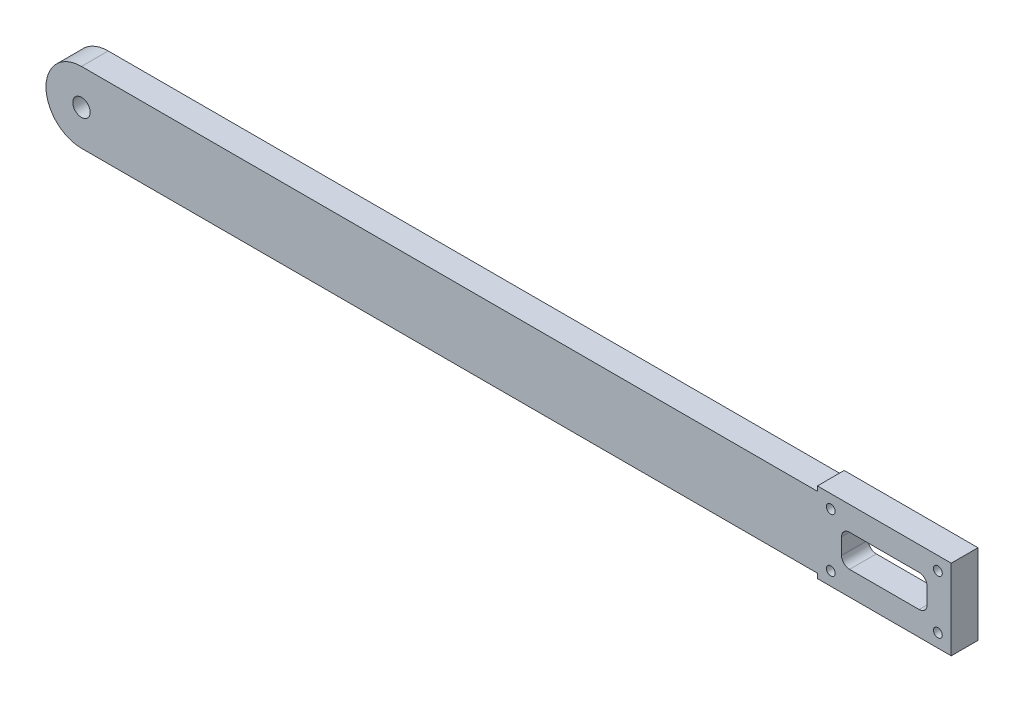
SolidWorks part; units mm, degrees
ref_plane "Front Plane" through (0, 0, 0) normal (0, 0, 1) x (1, 0, 0)
ref_plane "Top Plane" through (0, 0, 0) normal (0, 1, 0) x (1, 0, 0)
ref_plane "Right Plane" through (0, 0, 0) normal (1, 0, 0) x (0, 0, -1)
sketch "Sketch1" plane through (0, 0, 0) normal (0, 0, 1) x (1, 0, 0)
  line L0 (0, 0) -> (300, 0) construction
  line L1 (0, 13.25) -> (300, 13.25)
  line L2 (0, -13.25) -> (300, -13.25)
  line L3 (280, 10) -> (320, 10) construction
  line L4 (275, -15) -> (325, -15)
  line L5 (275, -15) -> (275, 15)
  line L6 (275, 15) -> (325, 15)
  line L7 (325, -15) -> (325, 15)
  line L8 (300, 15) -> (300, -15) construction
  line L9 (275, 0) -> (325, 0) construction
  line L10 (280, 10) -> (280, -10) construction
  line L12 (287, -6) -> (313, -6)
  line L13 (284, -3) -> (284, 3)
  line L14 (287, 6) -> (313, 6)
  line L15 (316, -3) -> (316, 3)
  line L16 (284, -6) -> (316, 6) construction
  line L17 (284, 6) -> (316, -6) construction
  arc A0 (0, 13.25) -> (0, -13.25) centre (0, 0) ccw
  arc A1 (300, -13.25) -> (300, 13.25) centre (300, 0) ccw
  circle A2 centre (0, 0) radius 3.25
  circle A3 centre (280, 10) radius 1.65
  circle A4 centre (320, 10) radius 1.65
  circle A5 centre (280, -10) radius 1.65
  circle A6 centre (320, -10) radius 1.65
  arc A7 (284, 3) -> (287, 6) centre (287, 3) cw
  arc A8 (316, 3) -> (313, 6) centre (313, 3) ccw
  arc A9 (313, -6) -> (316, -3) centre (313, -3) ccw
  arc A10 (287, -6) -> (284, -3) centre (287, -3) cw
  point P3 (150, 0)
  point P10 (300, 0)
  point P21 (300, 10)
  point P25 (280, 0)
  point P26 (300, 0)
  point P30 (300, 0)
  dimension "D1" = 6.5
  dimension "D2" = 10
  dimension "D4" = 3.3
  dimension "D11" = 3
  dimension "D3" = 300
  dimension "D5" = 40
  dimension "D6" = 20
  dimension "D7" = 5
  dimension "D8" = 5
  dimension "D9" = 4
  dimension "D10" = 4
extrude "Main Arm" add sketch "Sketch1" along normal blind 10 contours L1 A0 L2 L5 A2 | L2 A1 L1 L5 A3 A5 | A1 L2 L5 L4 L7 L6 L1 A6 A4 region at (132.8643, 0, 0) region at (275.5831, 14.125, 0) region at (287.5, 12.7964, 0)
